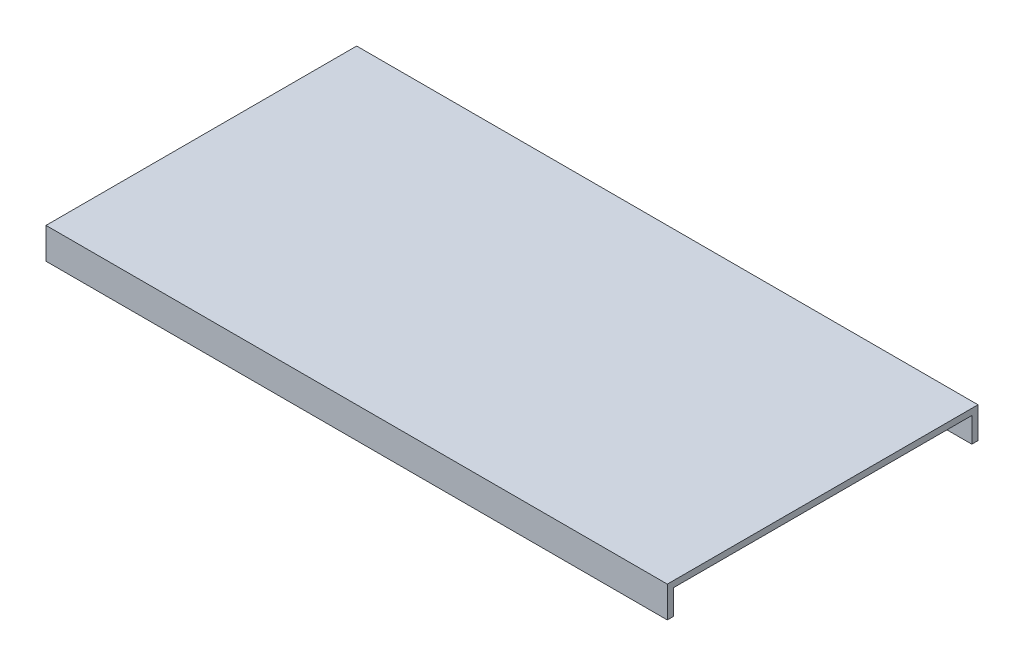
SolidWorks part; units mm, degrees
ref_plane "Ebene vorne" through (0, 0, 0) normal (0, 0, 1) x (1, 0, 0)
ref_plane "Ebene oben" through (0, 0, 0) normal (0, 1, 0) x (1, 0, 0)
ref_plane "Ebene rechts" through (0, 0, 0) normal (1, 0, 0) x (0, 0, -1)
sketch "Skizze1" plane through (0, 0, 0) normal (0, 0, 1) x (1, 0, 0)
  line L1 (0, 0) -> (1000, 0)
  line L2 (0, 0) -> (0, 50)
  line L3 (0, 50) -> (1000, 50)
  line L4 (1000, 0) -> (1000, 50)
  dimension "D1" = 50
  dimension "D2" = 1000
extrude "Aufsatz-Linear austragen1" add sketch "Skizze1" along normal blind 500
sketch "Skizze2" plane through (1000, 0, 0) normal (1, 0, 0) x (0, 0, -1)
  line L0 (-500, 0) -> (0, 0) construction
  line L1 (-490, 0) -> (-10, 0)
  line L2 (-490, 0) -> (-490, 40)
  line L3 (-490, 40) -> (-10, 40)
  line L4 (-10, 0) -> (-10, 40)
  line L5 (-500, 0) -> (-500, 50) construction
  line L6 (-500, 50) -> (0, 50) construction
  line L7 (0, 0) -> (0, 50) construction
  dimension "D1" = 10
  dimension "D2" = 10
  dimension "D3" = 10
extrude "Schnitt-Linear austragen1" cut sketch "Skizze2" against normal through all
